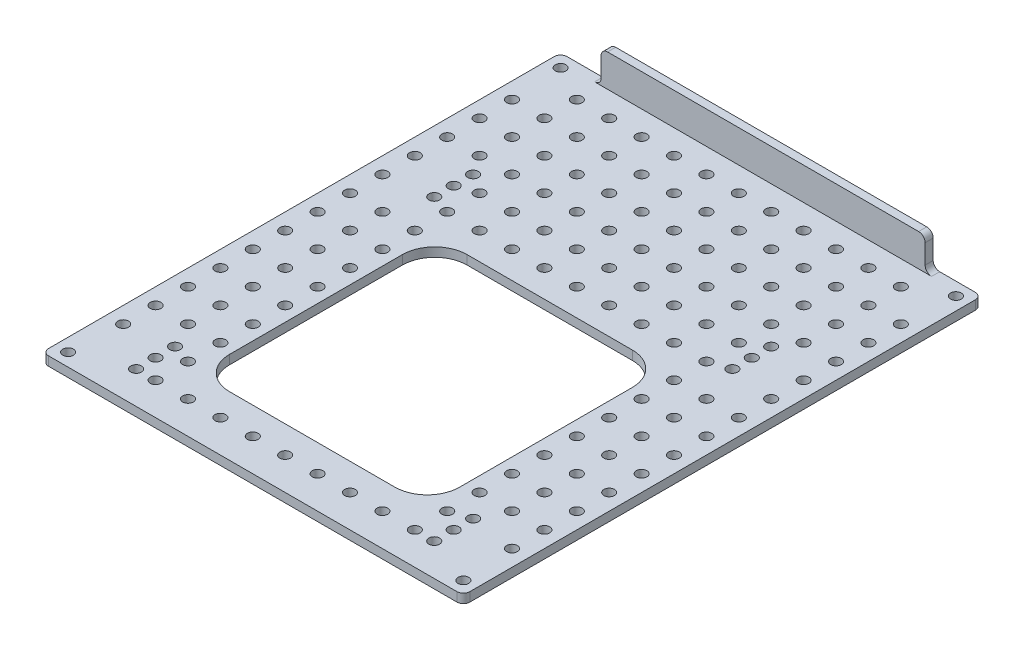
SolidWorks part; units mm, degrees
ref_plane "前视基准面" through (0, 0, 0) normal (0, 0, 1) x (1, 0, 0)
ref_plane "上视基准面" through (0, 0, 0) normal (0, 1, 0) x (1, 0, 0)
ref_plane "右视基准面" through (0, 0, 0) normal (1, 0, 0) x (0, 0, -1)
other "Configuration Table"
sketch "草图1" plane through (0, 0, 0) normal (0, 1, 0) x (1, 0, 0)
  line L1 (-65, 80) -> (65, 80)
  line L2 (-65, 80) -> (-65, -80)
  line L3 (-65, -80) -> (65, -80)
  line L4 (65, 80) -> (65, -80)
  line L5 (-65, 80) -> (65, -80) construction
  line L6 (-65, -80) -> (65, 80) construction
  point P0 (0, 0)
  dimension "D1" = 160
  dimension "D2" = 130
extrude "凸台-拉伸1" add sketch "草图1" along normal blind 2.8
sketch "草图2" plane through (0, 2.8, 0) normal (0, 1, 0) x (1, 0, 0)
  line L0 (0, 80) -> (0, -80) construction
  line L1 (65, 80) -> (-65, 80) construction
  line L2 (-65, -80) -> (65, -80) construction
  line L3 (-65, 0) -> (65, 0) construction
  line L4 (-65, 80) -> (-65, -80) construction
  line L5 (65, -80) -> (65, 80) construction
  circle A0 centre (-61, 76) radius 1.65
  circle A1 centre (61, 76) radius 1.65
  circle A2 centre (61, -76) radius 1.65
  circle A3 centre (-61, -76) radius 1.65
  dimension "D1" = 3.3
  dimension "D2" = 4
  dimension "D3" = 4
extrude "切除-拉伸1" cut sketch "草图2" against normal blind 3
sketch "草图3" plane through (0, 2.8, 0) normal (0, 1, 0) x (1, 0, 0)
  line L0 (0, 80) -> (0, -80) construction
  line L1 (65, 80) -> (-65, 80) construction
  line L2 (-65, -80) -> (65, -80) construction
  line L4 (-50, 26) -> (50, 26) construction
  line L5 (-50, 26) -> (-50, -74) construction
  line L6 (-50, -74) -> (50, -74) construction
  line L7 (50, 26) -> (50, -74) construction
  line L8 (-50, 26) -> (50, -74) construction
  line L9 (-50, -74) -> (50, 26) construction
  circle A0 centre (-46, 22) radius 1.65
  circle A1 centre (46, 22) radius 1.65
  circle A2 centre (46, -70) radius 1.65
  circle A3 centre (-46, -70) radius 1.65
  circle A4 centre (-46, 28) radius 1.65
  circle A5 centre (46, 28) radius 1.65
  circle A6 centre (-46, -64) radius 1.65
  circle A7 centre (46, -64) radius 1.65
  circle A8 centre (-46, 34) radius 1.65
  circle A9 centre (46, 34) radius 1.65
  circle A10 centre (-46, -58) radius 1.65
  circle A11 centre (46, -58) radius 1.65
  point P6 (0, -24)
  dimension "D2" = 3.3
  dimension "D1" = 100
  dimension "D3" = 4
  dimension "D4" = 6
  dimension "D6" = 3
  dimension "D5" = 4
extrude "切除-拉伸2" cut sketch "草图3" against normal blind 3
sketch "草图4" plane through (0, 2.8, 0) normal (0, 1, 0) x (1, 0, 0)
  line L0 (0, 80) -> (0, -80) construction
  line L1 (65, 80) -> (-65, 80) construction
  line L2 (-65, -80) -> (65, -80) construction
  circle A0 centre (0, 70) radius 1.65
  circle A1 centre (10, 70) radius 1.65
  circle A2 centre (20, 70) radius 1.65
  circle A3 centre (30, 70) radius 1.65
  circle A4 centre (40, 70) radius 1.65
  circle A5 centre (50, 70) radius 1.65
  circle A7 centre (-10, 70) radius 1.65
  circle A8 centre (-20, 70) radius 1.65
  circle A9 centre (-30, 70) radius 1.65
  circle A10 centre (-40, 70) radius 1.65
  circle A11 centre (-50, 70) radius 1.65
  circle A13 centre (0, 60) radius 1.65
  circle A14 centre (10, 60) radius 1.65
  circle A15 centre (20, 60) radius 1.65
  circle A16 centre (30, 60) radius 1.65
  circle A17 centre (40, 60) radius 1.65
  circle A18 centre (50, 60) radius 1.65
  circle A19 centre (-10, 60) radius 1.65
  circle A20 centre (-20, 60) radius 1.65
  circle A21 centre (-30, 60) radius 1.65
  circle A22 centre (-40, 60) radius 1.65
  circle A23 centre (-50, 60) radius 1.65
  circle A24 centre (0, 50) radius 1.65
  circle A25 centre (10, 50) radius 1.65
  circle A26 centre (20, 50) radius 1.65
  circle A27 centre (30, 50) radius 1.65
  circle A28 centre (40, 50) radius 1.65
  circle A29 centre (50, 50) radius 1.65
  circle A30 centre (-10, 50) radius 1.65
  circle A31 centre (-20, 50) radius 1.65
  circle A32 centre (-30, 50) radius 1.65
  circle A33 centre (-40, 50) radius 1.65
  circle A34 centre (-50, 50) radius 1.65
  circle A35 centre (0, 40) radius 1.65
  circle A36 centre (10, 40) radius 1.65
  circle A37 centre (20, 40) radius 1.65
  circle A38 centre (30, 40) radius 1.65
  circle A39 centre (40, 40) radius 1.65
  circle A40 centre (50, 40) radius 1.65
  circle A41 centre (-10, 40) radius 1.65
  circle A42 centre (-20, 40) radius 1.65
  circle A43 centre (-30, 40) radius 1.65
  circle A44 centre (-40, 40) radius 1.65
  circle A45 centre (-50, 40) radius 1.65
  circle A46 centre (0, 30) radius 1.65
  circle A47 centre (10, 30) radius 1.65
  circle A48 centre (20, 30) radius 1.65
  circle A49 centre (30, 30) radius 1.65
  circle A50 centre (40, 30) radius 1.65
  circle A52 centre (-10, 30) radius 1.65
  circle A53 centre (-20, 30) radius 1.65
  circle A54 centre (-30, 30) radius 1.65
  circle A55 centre (-40, 30) radius 1.65
  circle A57 centre (0, 20) radius 1.65
  circle A58 centre (10, 20) radius 1.65
  circle A59 centre (20, 20) radius 1.65
  circle A60 centre (30, 20) radius 1.65
  circle A61 centre (40, 20) radius 1.65
  circle A63 centre (-10, 20) radius 1.65
  circle A64 centre (-20, 20) radius 1.65
  circle A65 centre (-30, 20) radius 1.65
  circle A66 centre (-40, 20) radius 1.65
  circle A68 centre (0, 10) radius 1.65
  circle A69 centre (10, 10) radius 1.65
  circle A70 centre (20, 10) radius 1.65
  circle A71 centre (30, 10) radius 1.65
  circle A72 centre (40, 10) radius 1.65
  circle A73 centre (50, 10) radius 1.65
  circle A74 centre (-10, 10) radius 1.65
  circle A75 centre (-20, 10) radius 1.65
  circle A76 centre (-30, 10) radius 1.65
  circle A77 centre (-40, 10) radius 1.65
  circle A78 centre (-50, 10) radius 1.65
  circle A79 centre (0, 0) radius 1.65
  circle A80 centre (10, 0) radius 1.65
  circle A81 centre (20, 0) radius 1.65
  circle A82 centre (30, 0) radius 1.65
  circle A83 centre (40, 0) radius 1.65
  circle A84 centre (50, 0) radius 1.65
  circle A85 centre (-10, 0) radius 1.65
  circle A86 centre (-20, 0) radius 1.65
  circle A87 centre (-30, 0) radius 1.65
  circle A88 centre (-40, 0) radius 1.65
  circle A89 centre (-50, 0) radius 1.65
  circle A90 centre (0, -10) radius 1.65
  circle A91 centre (10, -10) radius 1.65
  circle A92 centre (20, -10) radius 1.65
  circle A93 centre (30, -10) radius 1.65
  circle A94 centre (40, -10) radius 1.65
  circle A95 centre (50, -10) radius 1.65
  circle A96 centre (-10, -10) radius 1.65
  circle A97 centre (-20, -10) radius 1.65
  circle A98 centre (-30, -10) radius 1.65
  circle A99 centre (-40, -10) radius 1.65
  circle A100 centre (-50, -10) radius 1.65
  circle A101 centre (0, -20) radius 1.65
  circle A102 centre (10, -20) radius 1.65
  circle A103 centre (20, -20) radius 1.65
  circle A104 centre (30, -20) radius 1.65
  circle A105 centre (40, -20) radius 1.65
  circle A106 centre (50, -20) radius 1.65
  circle A107 centre (-10, -20) radius 1.65
  circle A108 centre (-20, -20) radius 1.65
  circle A109 centre (-30, -20) radius 1.65
  circle A110 centre (-40, -20) radius 1.65
  circle A111 centre (-50, -20) radius 1.65
  circle A112 centre (0, -30) radius 1.65
  circle A113 centre (10, -30) radius 1.65
  circle A114 centre (20, -30) radius 1.65
  circle A115 centre (30, -30) radius 1.65
  circle A116 centre (40, -30) radius 1.65
  circle A117 centre (50, -30) radius 1.65
  circle A118 centre (-10, -30) radius 1.65
  circle A119 centre (-20, -30) radius 1.65
  circle A120 centre (-30, -30) radius 1.65
  circle A121 centre (-40, -30) radius 1.65
  circle A122 centre (-50, -30) radius 1.65
  circle A123 centre (0, -40) radius 1.65
  circle A124 centre (10, -40) radius 1.65
  circle A125 centre (20, -40) radius 1.65
  circle A126 centre (30, -40) radius 1.65
  circle A127 centre (40, -40) radius 1.65
  circle A128 centre (50, -40) radius 1.65
  circle A129 centre (-10, -40) radius 1.65
  circle A130 centre (-20, -40) radius 1.65
  circle A131 centre (-30, -40) radius 1.65
  circle A132 centre (-40, -40) radius 1.65
  circle A133 centre (-50, -40) radius 1.65
  circle A134 centre (0, -50) radius 1.65
  circle A135 centre (10, -50) radius 1.65
  circle A136 centre (20, -50) radius 1.65
  circle A137 centre (30, -50) radius 1.65
  circle A138 centre (40, -50) radius 1.65
  circle A139 centre (50, -50) radius 1.65
  circle A140 centre (-10, -50) radius 1.65
  circle A141 centre (-20, -50) radius 1.65
  circle A142 centre (-30, -50) radius 1.65
  circle A143 centre (-40, -50) radius 1.65
  circle A144 centre (-50, -50) radius 1.65
  circle A145 centre (0, -60) radius 1.65
  circle A146 centre (10, -60) radius 1.65
  circle A147 centre (20, -60) radius 1.65
  circle A148 centre (30, -60) radius 1.65
  circle A149 centre (40, -60) radius 1.65
  circle A151 centre (-10, -60) radius 1.65
  circle A152 centre (-20, -60) radius 1.65
  circle A153 centre (-30, -60) radius 1.65
  circle A154 centre (-40, -60) radius 1.65
  circle A156 centre (0, -70) radius 1.65
  circle A157 centre (10, -70) radius 1.65
  circle A158 centre (20, -70) radius 1.65
  circle A159 centre (30, -70) radius 1.65
  circle A160 centre (40, -70) radius 1.65
  circle A162 centre (-10, -70) radius 1.65
  circle A163 centre (-20, -70) radius 1.65
  circle A164 centre (-30, -70) radius 1.65
  circle A165 centre (-40, -70) radius 1.65
  circle A167 centre (-50, 30) radius 1.65 [skipped]
  circle A168 centre (-50, 20) radius 1.65 [skipped]
  circle A169 centre (50, 30) radius 1.65 [skipped]
  circle A170 centre (50, 20) radius 1.65 [skipped]
  circle A171 centre (-50, -60) radius 1.65 [skipped]
  circle A172 centre (-50, -70) radius 1.65 [skipped]
  circle A173 centre (50, -70) radius 1.65 [skipped]
  circle A174 centre (50, -60) radius 1.65 [skipped]
  circle A175 centre (-60, 60) radius 1.65
  circle A176 centre (-60, 50) radius 1.65
  circle A177 centre (-60, 40) radius 1.65
  circle A178 centre (-60, 30) radius 1.65
  circle A179 centre (-60, 20) radius 1.65
  circle A180 centre (-60, 10) radius 1.65
  circle A181 centre (-60, 0) radius 1.65
  circle A182 centre (-60, -10) radius 1.65
  circle A183 centre (-60, -20) radius 1.65
  circle A184 centre (-60, -30) radius 1.65
  circle A185 centre (-60, -40) radius 1.65
  circle A186 centre (-60, -50) radius 1.65
  circle A187 centre (-60, -60) radius 1.65
  circle A188 centre (60, -60) radius 1.65
  circle A189 centre (60, -50) radius 1.65
  circle A190 centre (60, -40) radius 1.65
  circle A191 centre (60, -30) radius 1.65
  circle A192 centre (60, -20) radius 1.65
  circle A193 centre (60, -10) radius 1.65
  circle A194 centre (60, 0) radius 1.65
  circle A195 centre (60, 10) radius 1.65
  circle A196 centre (60, 20) radius 1.65
  circle A197 centre (60, 30) radius 1.65
  circle A198 centre (60, 40) radius 1.65
  circle A199 centre (60, 50) radius 1.65
  circle A200 centre (60, 60) radius 1.65
  dimension "D1" = 3.3
  dimension "D2" = 10
  dimension "D3" = 6
  dimension "D4" = 6
  dimension "D5" = 15
  dimension "D6" = 2
extrude "切除-拉伸3" cut sketch "草图4" against normal blind 3
sketch "草图5" plane through (0, 2.8, 0) normal (0, 1, 0) x (1, 0, 0)
  line L0 (0, 80) -> (0, -80) construction
  line L1 (65, 80) -> (-65, 80) construction
  line L2 (-65, -80) -> (65, -80) construction
  line L3 (-65, 80) -> (-65, -80) construction
  line L4 (50, 77.5) -> (-50, 77.5)
  line L5 (50, 77.5) -> (50, 80)
  line L6 (50, 80) -> (-50, 80)
  line L7 (-50, 77.5) -> (-50, 80)
  line L8 (50, 77.5) -> (-50, 80) construction
  line L9 (50, 80) -> (-50, 77.5) construction
  point P6 (0, 78.75)
  dimension "D1" = 2.5
  dimension "D2" = 15
extrude "凸台-拉伸2" add sketch "草图5" along normal blind 10
sketch "草图6" plane through (0, 2.8, 0) normal (0, 1, 0) x (1, 0, 0)
  line L0 (0, 77.5) -> (0, -80) construction
  line L1 (-50, 77.5) -> (50, 77.5) construction
  line L2 (-65, -80) -> (65, -80) construction
  line L4 (35.5, 11.65) -> (-35.5, 11.65)
  line L5 (35.5, 11.65) -> (35.5, -61.65)
  line L6 (35.5, -61.65) -> (-35.5, -61.65)
  line L7 (-35.5, 11.65) -> (-35.5, -61.65)
  line L8 (35.5, 11.65) -> (-35.5, -61.65) construction
  line L9 (35.5, -61.65) -> (-35.5, 11.65) construction
  circle A0 centre (-10, -60) radius 1.65 construction
  circle A1 centre (-10, 10) radius 1.65 construction
  point P6 (0, -25)
  dimension "D1" = 71
extrude "切除-拉伸4" cut sketch "草图6" against normal blind 10
fillet "圆角1" radius 10 4 edges at (-35.5, 1.4, 61.65) (35.5, 1.4, 61.65) (35.5, 1.4, -11.65) (-35.5, 1.4, -11.65)
fillet "圆角2" radius 2 8 edges at (65, 1.4, 80) (-65, 1.4, 80) (65, 1.4, -80) (-65, 1.4, -80) (-50, 2.8, -78.75) (50, 2.8, -78.75) (50, 12.8, -78.75) (-50, 12.8, -78.75)
